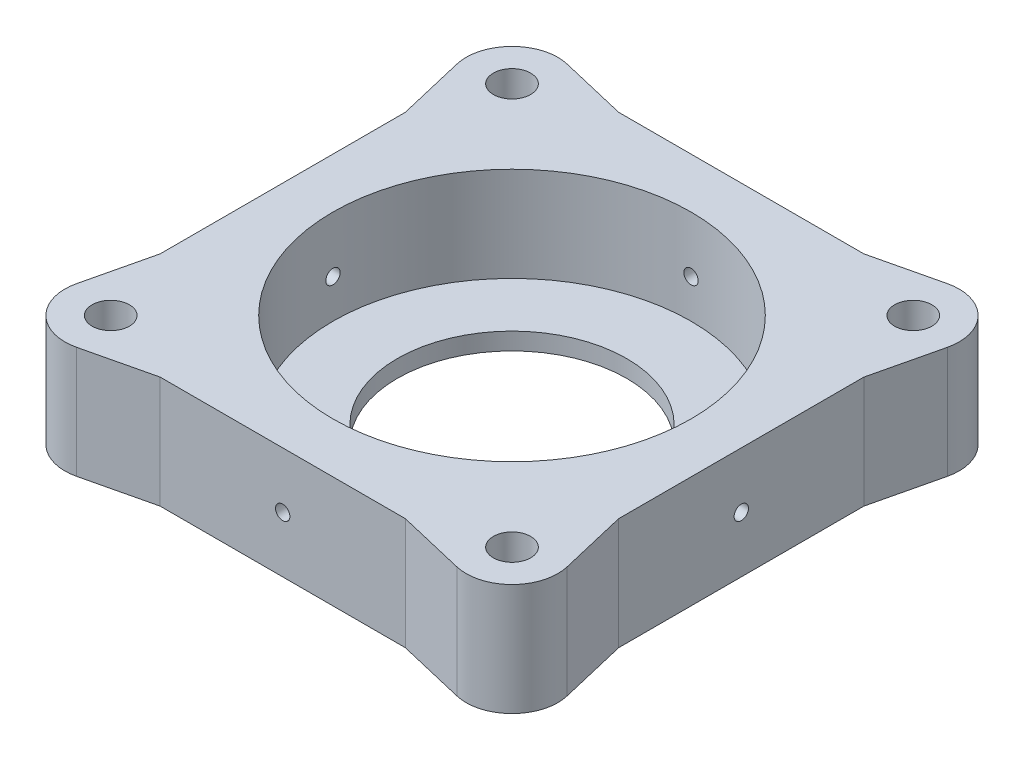
SolidWorks part; units mm, degrees
ref_plane "Front Plane" through (0, 0, 0) normal (0, 0, 1) x (1, 0, 0)
ref_plane "Top Plane" through (0, 0, 0) normal (0, 1, 0) x (1, 0, 0)
ref_plane "Right Plane" through (0, 0, 0) normal (1, 0, 0) x (0, 0, -1)
sketch "Sketch1" plane through (0, 0, 0) normal (0, 1, 0) x (1, 0, 0)
  line L0 (0, 35) -> (0, -35) construction
  line L1 (35, -35) -> (-35, -35)
  line L2 (35, -35) -> (35, 35)
  line L3 (35, 35) -> (-35, 35)
  line L4 (-35, -35) -> (-35, 35)
  line L5 (35, -35) -> (-35, 35) construction
  line L6 (35, 35) -> (-35, -35) construction
  line L7 (-35, 0) -> (35, 0) construction
  line L8 (-33.1578, 42.785) -> (7.8292, 33.0863)
  line L9 (-42.785, 33.1578) -> (-33.0863, -7.8292)
  line L10 (42.785, 33.1578) -> (33.0863, -7.8292)
  line L11 (33.1578, 42.785) -> (-7.8292, 33.0863)
  line L12 (-42.785, -33.1578) -> (-33.0863, 7.8292)
  line L13 (-33.1578, -42.785) -> (7.8292, -33.0863)
  line L14 (33.1578, -42.785) -> (-7.8292, -33.0863)
  line L15 (42.785, -33.1578) -> (33.0863, 7.8292)
  line L17 (40, -40) -> (-40, -40)
  line L18 (40, -40) -> (40, 40)
  line L19 (40, 40) -> (-40, 40)
  line L20 (-40, -40) -> (-40, 40)
  line L21 (40, -40) -> (-40, 40) construction
  line L22 (40, 40) -> (-40, -40) construction
  circle A0 centre (0, 0) radius 20
  circle A1 centre (0, 0) radius 34
  circle A2 centre (-35, 35) radius 3.25
  circle A3 centre (0, 0) radius 40
  circle A4 centre (-35, 35) radius 8
  circle A5 centre (35, 35) radius 3.25
  circle A6 centre (35, 35) radius 8
  circle A7 centre (-35, -35) radius 3.25
  circle A8 centre (-35, -35) radius 8
  circle A9 centre (35, -35) radius 3.25
  circle A10 centre (35, -35) radius 8
  dimension "D1" = 40
  dimension "D2" = 68
  dimension "D3" = 6.5
  dimension "D5" = 80
  dimension "D4" = 16
  dimension "D6" = 70
extrude "Boss-Extrude1" add sketch "Sketch1" along normal blind 19.5 contours L19 A4 L20 | L3 A4 L19 L20 L4 A2 | L4 A4 L3 A2 | A4 L9 L20 | A4 L20 L9 A3 L4 | A3 L9 L20 | L4 A3 L9 | L9 A3 L12 L4 | A3 L20 L12 | L12 A3 L4 | L20 A8 L4 A3 L12 | L12 A8 L20 | A8 L17 L20 | A8 L20 L17 L1 A7 L4 | A8 L4 A7 L1 | L4 A8 L1 A3 | L4 A3 L1 L13 L14 A1 L9 L12 | L3 A3 L4 L9 L12 A1 L11 L8 | A1 L12 L9 | A4 L4 A3 L3 | A4 L3 A3 L8 L19 | A4 L19 L8 | A3 L19 L8 | L8 A3 L3 | L11 A3 L8 L3 | A1 L8 L11 | L3 A3 L11 | L2 A3 L3 L11 L8 A1 L15 L10 | L3 A6 L19 L11 A3 | A3 L11 L19 | L19 A6 L11 | L2 A6 L3 A3 | A6 L2 A5 L3 | A6 L3 A5 L2 L18 L19 | A6 L19 L18 | L10 A6 L18 | L18 A6 L2 A3 L10 | A3 L18 L10 | L10 A3 L2 | L15 A3 L10 L2 | A3 L15 L18 | L2 A3 L15 | A1 L10 L15 | L1 A3 L2 L15 L10 A1 L13 L14 | A10 L18 L15 A3 L2 | A10 L15 L18 | A10 L2 A3 L1 | L18 A10 L2 A9 L1 L17 | L2 A10 L1 A9 | A10 L18 L17 | A10 L17 L14 | A10 L1 A3 L14 L17 | L14 A3 L1 | A3 L17 L14 | A3 L14 L1 L13 | A1 L14 L13 | L1 A3 L13 | A3 L13 L17 | L1 A8 L17 L13 A3 | L17 A8 L13 | A1 A0 | L11 L3 L8 | L15 L2 L10 | L1 L14 L13 | L4 L12 L9 region at (-27.625, 0, 37.5886) region at (-28.9419, 0, 28.9419) region at (-31.2062, 0, 31.2062) region at (-21.8672, 0, 37.555) region at (-24.6184, 0, 24.6184) region at (-10.9152, 0, 35.995) region at (-37.555, 0, 21.8672) region at (-30.8311, 0, 41.5907) region at (-27.2274, 0, 40.8217) region at (0, 0, 34.9796) region at (0, 0, 37.8149) region at (-35.995, 0, 10.9152) region at (-12.614, 0, 39.3478) region at (-40.8217, 0, 27.2274) region at (24.6184, 0, 24.6184) region at (10.9152, 0, 35.995) region at (0, 0, 34.191) region at (-37.8149, 0, 0) region at (-34.9796, 0, 0) region at (-39.3478, 0, 12.614) region at (12.614, 0, 39.3478) region at (28.9419, 0, 28.9419) region at (21.8672, 0, 37.555) region at (0, 0, 33.0383) region at (-35.995, 0, -10.9152) region at (-24.6184, 0, -24.6184) region at (-34.191, 0, 0) region at (-39.3478, 0, -12.614) region at (27.2274, 0, 40.8217) region at (31.2062, 0, 31.2062) region at (29.375, 0, 35.1838) region at (37.555, 0, 21.8672) region at (35.995, 0, 10.9152) region at (34.191, 0, 0) region at (-37.555, 0, -21.8672) region at (-28.9419, 0, -28.9419) region at (-40.8217, 0, -27.2274) region at (30.8311, 0, 41.5907) region at (34.9796, 0, 0) region at (37.8149, 0, 0) region at (39.3478, 0, 12.614) region at (24.6184, 0, -24.6184) region at (-37.5886, 0, -27.625) region at (-31.2062, 0, -31.2062) region at (-10.9152, 0, -35.995) region at (-21.8672, 0, -37.555) region at (0, 0, -34.191) region at (-40.5144, 0, -40.5144) region at (40.8217, 0, 27.2274) region at (35.995, 0, -10.9152) region at (39.3478, 0, -12.614) region at (0, 0, -37.8149) region at (0, 0, -34.9796) region at (-12.614, 0, -39.3478) region at (-27.2274, 0, -40.8217) region at (28.9419, 0, -28.9419) region at (37.555, 0, -21.8672) region at (40.8217, 0, -27.2274) region at (10.9152, 0, -35.995) region at (12.614, 0, -39.3478)
sketch "Sketch2" plane through (0, 19.5, 0) normal (0, 1, 0) x (1, 0, 0)
  circle A0 centre (0, 0) radius 31.25
  dimension "D1" = 62.5
extrude "Cut-Extrude1" cut sketch "Sketch2" against normal blind 16.5
sketch "Sketch3" plane through (0, 0, 0) normal (0, -1, 0) x (1, 0, 0)
  circle A0 centre (-35, 35) radius 5.25
  circle A1 centre (35, 35) radius 5.25
  circle A2 centre (35, -35) radius 5.25
  circle A3 centre (-35, -35) radius 5.25
  dimension "D1" = 10.5
extrude "Cut-Extrude2" cut sketch "Sketch3" against normal blind 10
sketch "Sketch4" plane through (0, 0, 40) normal (0, 0, 1) x (1, 0, 0)
  line L0 (0, 0) -> (0, 19.5) construction
  line L1 (21.3883, 0) -> (-21.3883, 0) construction
  line L2 (21.3883, 19.5) -> (-21.3883, 19.5) construction
  circle A0 centre (0, 9.75) radius 1.25
  dimension "D1" = 2.5
extrude "Cut-Extrude3" cut sketch "Sketch4" against normal up to surface (80 mm away) up to face at (0, 9.75, -40)
sketch "Sketch5" plane through (40, 0, 0) normal (1, 0, 0) x (0, 0, -1)
  line L0 (0, 0) -> (0, 19.5) construction
  line L1 (-21.3883, 19.5) -> (21.3883, 19.5) construction
  line L2 (-21.3883, 0) -> (21.3883, 0) construction
  circle A0 centre (0, 9.75) radius 1.25
  point P7 (0, 8.6818)
  point P8 (0, 0)
  dimension "D1" = 2.5
extrude "Cut-Extrude4" cut sketch "Sketch5" against normal up to surface (80 mm away) up to face at (-40, 9.75, 0)
sketch "Sketch6" [suppressed] plane through (0, 19.5, 0) normal (0, 1, 0) x (1, 0, 0)
  line L12 (21.3883, -40) -> (33.1578, -42.785)
  line L13 (42.785, -33.1578) -> (40, -21.3883)
  line L14 (40, -21.3883) -> (40, 21.3883)
  line L15 (40, 21.3883) -> (42.785, 33.1578)
  line L16 (33.1578, 42.785) -> (21.3883, 40)
  line L17 (21.3883, 40) -> (-21.3883, 40)
  line L18 (-21.3883, 40) -> (-33.1578, 42.785)
  line L19 (-42.785, 33.1578) -> (-40, 21.3883)
  line L20 (-40, 21.3883) -> (-40, -21.3883)
  line L21 (-40, -21.3883) -> (-42.785, -33.1578)
  line L22 (-33.1578, -42.785) -> (-21.3883, -40)
  line L23 (-21.3883, -40) -> (21.3883, -40)
  line L24 (21.3883, -40) -> (33.1578, -42.785)
  line L25 (42.785, -33.1578) -> (40, -21.3883)
  line L26 (40, -21.3883) -> (40, 21.3883)
  line L27 (40, 21.3883) -> (42.785, 33.1578)
  line L28 (33.1578, 42.785) -> (21.3883, 40)
  line L29 (21.3883, 40) -> (-21.3883, 40)
  line L30 (-21.3883, 40) -> (-33.1578, 42.785)
  line L31 (-42.785, 33.1578) -> (-40, 21.3883)
  line L32 (-40, 21.3883) -> (-40, -21.3883)
  line L33 (-40, -21.3883) -> (-42.785, -33.1578)
  line L34 (-33.1578, -42.785) -> (-21.3883, -40)
  line L35 (-21.3883, -40) -> (21.3883, -40)
  circle A0 centre (0, 0) radius 31.25 construction
  circle A1 centre (35, 35) radius 3.25 construction
  circle A2 centre (-35, 35) radius 3.25 construction
  circle A3 centre (35, -35) radius 3.25 construction
  arc A4 (33.1578, -42.785) -> (42.785, -33.1578) centre (35, -35) ccw
  arc A5 (42.785, 33.1578) -> (33.1578, 42.785) centre (35, 35) ccw
  arc A6 (-33.1578, 42.785) -> (-42.785, 33.1578) centre (-35, 35) ccw
  arc A7 (-42.785, -33.1578) -> (-33.1578, -42.785) centre (-35, -35) ccw
  arc A8 (33.1578, -42.785) -> (42.785, -33.1578) centre (35, -35) ccw
  arc A9 (42.785, 33.1578) -> (33.1578, 42.785) centre (35, 35) ccw
  arc A10 (-33.1578, 42.785) -> (-42.785, 33.1578) centre (-35, 35) ccw
  arc A11 (-42.785, -33.1578) -> (-33.1578, -42.785) centre (-35, -35) ccw
  circle A12 centre (-35, -35) radius 3.25 construction
  circle A13 centre (0, 0) radius 31.25
  circle A14 centre (35, 35) radius 3.25
  circle A15 centre (-35, 35) radius 3.25
  circle A16 centre (35, -35) radius 3.25
  circle A17 centre (-35, -35) radius 3.25
  dimension "D1" = 0
extrude "Boss-Extrude4" [suppressed] add sketch "Sketch6" along normal blind 3.5
sketch "Sketch7" [suppressed] plane through (0, 0, 0) normal (0, -1, 0) x (1, 0, 0)
  line L0 (-35, 35) -> (-38.7123, 38.7123) construction
  line L1 (-29.1444, 33.431) -> (-30.7134, 39.2866)
  line L2 (-30.7134, 39.2866) -> (-36.569, 40.8556)
  line L3 (-36.569, 40.8556) -> (-40.8556, 36.569)
  line L4 (-40.8556, 36.569) -> (-39.2866, 30.7134)
  line L5 (-39.2866, 30.7134) -> (-33.431, 29.1444)
  line L6 (-33.431, 29.1444) -> (-29.1444, 33.431)
  line L7 (39.2866, 30.7134) -> (40.8556, 36.569)
  line L8 (40.8556, 36.569) -> (36.569, 40.8556)
  line L9 (36.569, 40.8556) -> (30.7134, 39.2866)
  line L10 (30.7134, 39.2866) -> (29.1444, 33.431)
  line L11 (29.1444, 33.431) -> (33.431, 29.1444)
  line L12 (33.431, 29.1444) -> (39.2866, 30.7134)
  line L13 (30.7134, -39.2866) -> (36.569, -40.8556)
  line L14 (36.569, -40.8556) -> (40.8556, -36.569)
  line L15 (40.8556, -36.569) -> (39.2866, -30.7134)
  line L16 (39.2866, -30.7134) -> (33.431, -29.1444)
  line L17 (33.431, -29.1444) -> (29.1444, -33.431)
  line L18 (29.1444, -33.431) -> (30.7134, -39.2866)
  line L19 (-39.2866, -30.7134) -> (-40.8556, -36.569)
  line L20 (-40.8556, -36.569) -> (-36.569, -40.8556)
  line L21 (-36.569, -40.8556) -> (-30.7134, -39.2866)
  line L22 (-30.7134, -39.2866) -> (-29.1444, -33.431)
  line L23 (-29.1444, -33.431) -> (-33.431, -29.1444)
  line L24 (-33.431, -29.1444) -> (-39.2866, -30.7134)
  line L25 (0, 40) -> (0, -40) construction
  line L26 (21.3883, 40) -> (-21.3883, 40) construction
  line L27 (21.3883, -40) -> (-21.3883, -40) construction
  circle A0 centre (-35, 35) radius 5.25 construction
  point P32 (0, 0)
  dimension "D1" = 10.5
  dimension "D2" = 4
extrude "Cut-Extrude5" [suppressed] cut sketch "Sketch7" against normal offset from surface (21.5 mm away) 1.5 up to face at (35, 0, 29.75)
